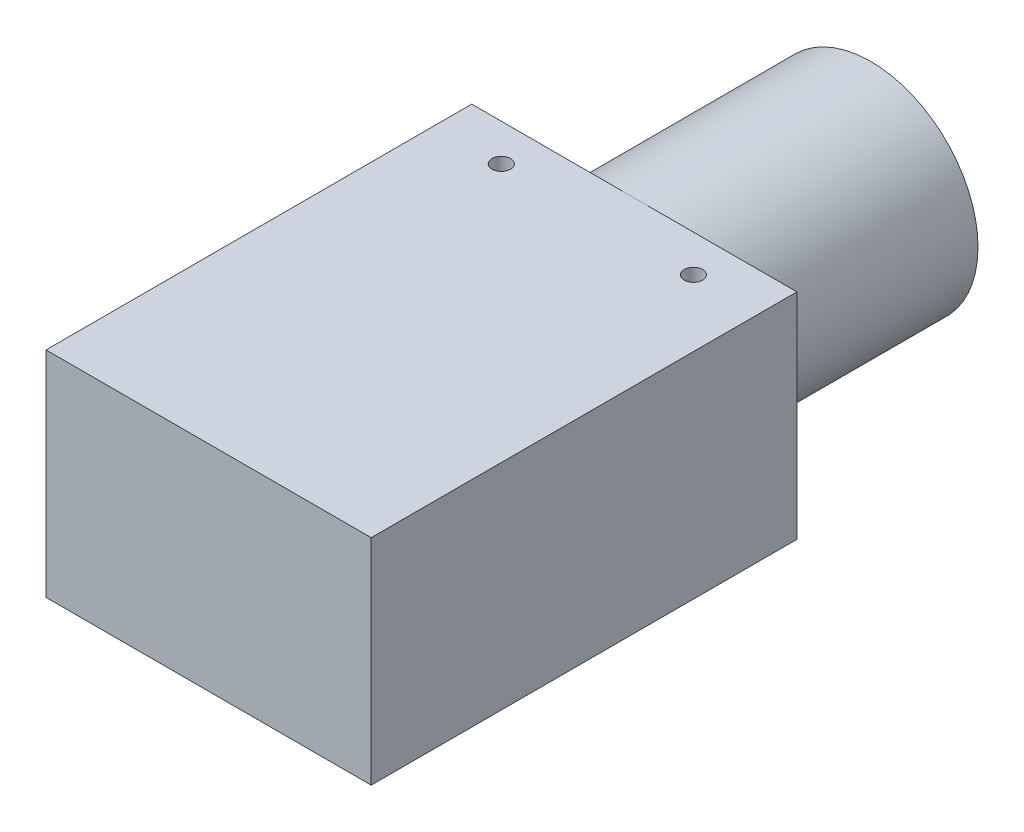
SolidWorks part; units mm, degrees
ref_plane "Front Plane" through (0, 0, 0) normal (0, 0, 1) x (1, 0, 0)
ref_plane "Top Plane" through (0, 0, 0) normal (0, 1, 0) x (1, 0, 0)
ref_plane "Right Plane" through (0, 0, 0) normal (1, 0, 0) x (0, 0, -1)
sketch "Sketch1" plane through (0, 0, 0) normal (0, 0, 1) x (1, 0, 0)
  line L1 (-22, -14.5) -> (22, -14.5)
  line L2 (-22, -14.5) -> (-22, 14.5)
  line L3 (-22, 14.5) -> (22, 14.5)
  line L4 (22, -14.5) -> (22, 14.5)
  line L5 (-22, -14.5) -> (22, 14.5) construction
  line L6 (-22, 14.5) -> (22, -14.5) construction
  point P0 (0, 0)
  dimension "D1" = 29
  dimension "D2" = 44
extrude "Boss-Extrude1" add sketch "Sketch1" along normal blind 57.6
sketch "Sketch2" plane through (0, 0, 0) normal (0, 0, 1) x (1, 0, 0)
  circle A0 centre (0, 0) radius 14.5
extrude "Boss-Extrude2" add sketch "Sketch2" against normal blind 32
hole_wizard "M3x0.5 Tapped Hole1" positions "Sketch3" profile "Sketch4" tap size "M3x0.5" standard "ANSI Metric"
sketch "Sketch3" plane through (0, 14.5, 0) normal (0, 1, 0) x (1, 0, 0)
  line L0 (-13, -5) -> (13, -5) construction
  point P0 (-13, -5)
  point P2 (13, -5)
  point P9 (0, -5)
  dimension "D1" = 26
  dimension "D2" = 5
sketch "Sketch4" plane through (-13, 14.5, 5) normal (1, 0, 0) x (0, 0, 1)
  line L0 (0, 0) -> (0, 3.7511)
  line L1 (0, 3.7511) -> (1.25, 3)
  line L2 (1.25, 3) -> (1.25, 0)
  line L5 (1.25, 0) -> (0, 0)
  line L10 (0, 3.7511) -> (-1.25, 3) construction
  line L11 (0, -6.35) -> (0, 107.95) construction
  dimension "Tap Drill Dia." = 2.5
  dimension "Tap Drill Depth" = 3
  dimension "Drill Angle" = 118
cosmetic thread "Hole Thread1" parameters "D1"=3, "D2"=3
cosmetic thread "Hole Thread2" parameters "D1"=3, "D2"=3
ref_axis "Axis1" through (0, 0, -32) along (0, 0, 1)
